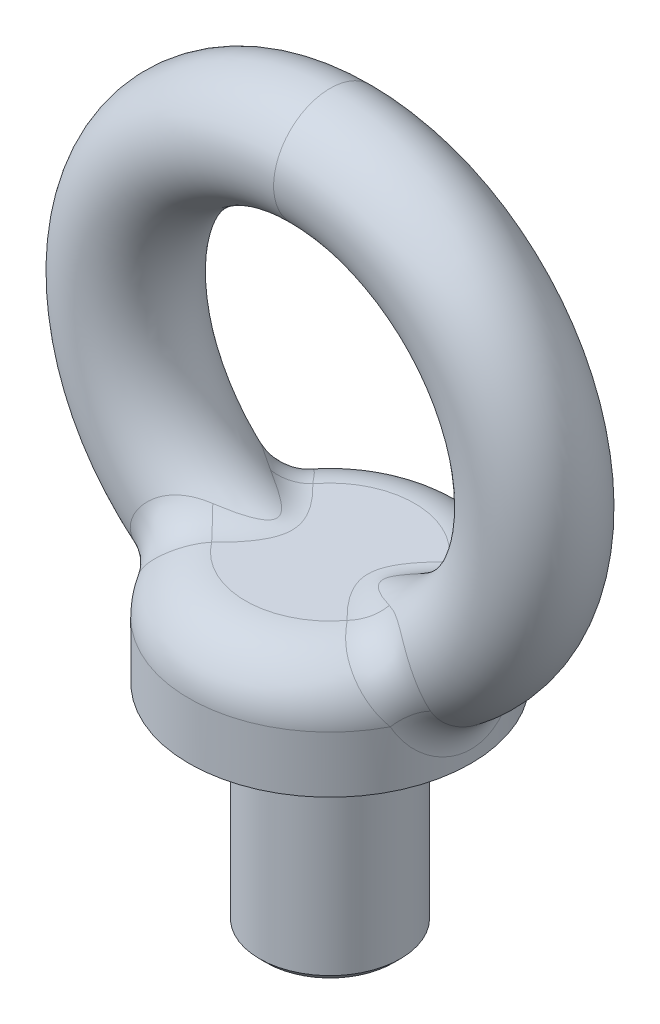
SolidWorks part; units mm, degrees
ref_plane "Front Plane" through (0, 0, 0) normal (0, 0, 1) x (1, 0, 0)
ref_plane "Top Plane" through (0, 0, 0) normal (0, 1, 0) x (1, 0, 0)
ref_plane "Right Plane" through (0, 0, 0) normal (1, 0, 0) x (0, 0, -1)
sketch "Sketch1" plane through (0, 0, 0) normal (0, 1, 0) x (1, 0, 0)
  circle A0 centre (0, 0) radius 10
  dimension "D1" = 20
extrude "Boss-Extrude1" add sketch "Sketch1" along normal blind 30 contours A0
cosmetic thread "Cosmetic Thread3" parameters "D1"=25, "D2"=17.252
sketch "Sketch2" plane through (0, 0, 0) normal (0, 0, 1) x (1, 0, 0)
  line L0 (0, 30) -> (20, 30)
  line L1 (10, 30) -> (-10, 30) construction
  line L2 (20, 30) -> (20, 38)
  line L3 (0, 46) -> (12, 46)
  line L4 (0, 0) -> (0, 46) construction
  line L5 (0, 30) -> (0, 46)
  arc A0 (12, 46) -> (20, 38) centre (12, 38) cw
  dimension "D1" = 8
  dimension "D2" = 20
  dimension "D3" = 16
revolve "Revolve10" add sketch "Sketch2" angle 360 about L4
chamfer "Chamfer1" distance 1 angle 45 1 edges at (0, 0, 10)
sketch "Sketch3" plane through (0, 0, 0) normal (0, 0, 1) x (1, 0, 0)
  line L2 (-10, 30) -> (10, 30) construction
  circle A1 centre (0, 66) radius 29
  dimension "D1" = 36
  dimension "D3" = 58
sketch "Sketch4" plane through (0, 0, 0) normal (1, 0, 0) x (0, 0, -1)
  line L0 (0, 95) -> (0, 37) construction
  circle A0 centre (0, 95) radius 8
  dimension "D1" = 16
sweep "Sweep1" add profiles "Sketch4" path "Sketch3"
fillet "Fillet2" radius 6 8 edges at (19.9972, 34.8778, -0.3356) (-19.9972, 34.8778, 0.3356) (15.7859, 43.6955, 7.8228) (-15.7859, 43.6955, -7.8228) (15.4457, 44.0256, -7.7084) (-15.4457, 44.0256, 7.7084) (-30.9692, 46, -1.4588) (31.1228, 46, -0.2822)
